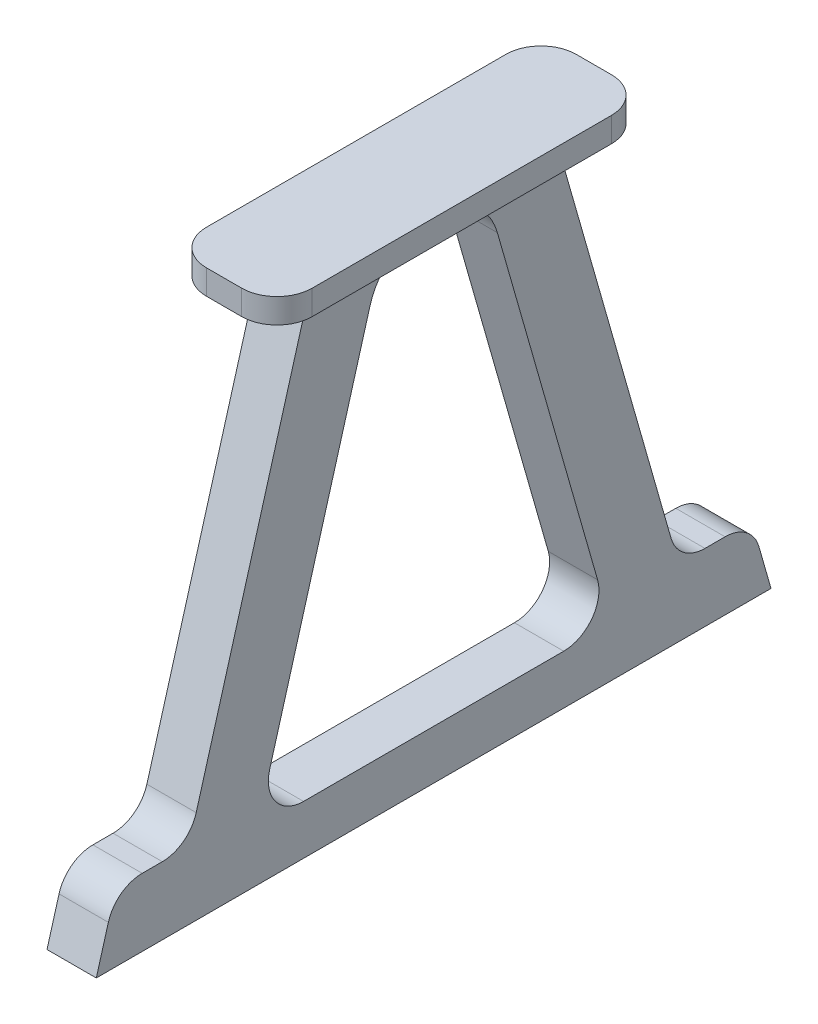
SolidWorks part; units mm, degrees
ref_plane "Front Plane" through (0, 0, 0) normal (0, 0, 1) x (1, 0, 0)
ref_plane "Top Plane" through (0, 0, 0) normal (0, 1, 0) x (1, 0, 0)
ref_plane "Right Plane" through (0, 0, 0) normal (1, 0, 0) x (0, 0, -1)
sketch "Sketch10" plane through (0, 0, 0) normal (0, 1, 0) x (1, 0, 0)
  line L5 (-5, -52.5) -> (5, -52.5)
  line L6 (-15, -42.5) -> (-15, 42.5)
  line L7 (-5, 52.5) -> (5, 52.5)
  line L8 (15, -42.5) -> (15, 42.5)
  line L9 (-15, -52.5) -> (15, 52.5) construction
  line L10 (-15, 52.5) -> (15, -52.5) construction
  arc A4 (5, -52.5) -> (15, -42.5) centre (5, -42.5) ccw
  arc A5 (-5, -52.5) -> (-15, -42.5) centre (-5, -42.5) cw
  arc A6 (5, 52.5) -> (15, 42.5) centre (5, 42.5) cw
  arc A7 (-15, 42.5) -> (-5, 52.5) centre (-5, 42.5) cw
  point P0 (0, 0)
  dimension "D3" = 10
  dimension "D1" = 105
  dimension "D2" = 30
extrude "Boss-Extrude3" add sketch "Sketch10" against normal blind 7
sketch "Sketch11" plane through (0, 0, 0) normal (1, 0, 0) x (0, 0, -1)
  line L0 (-35, -7) -> (35, -7)
  line L1 (-42.5, -7) -> (42.5, -7) construction
  line L2 (0, 0) -> (0, -258.7545) construction
  line L3 (-35, -7) -> (-75, -147)
  line L4 (-75, -147) -> (75, -147)
  line L5 (35, -7) -> (75, -147)
  line L6 (-75, -147) -> (-95.8003, -147)
  line L7 (-95.8003, -147) -> (-90.3059, -127.7695)
  line L8 (-90.3059, -127.7695) -> (-69.5056, -127.7695)
  line L9 (-71, -133) -> (71, -133)
  line L10 (69.5056, -127.7695) -> (90.3059, -127.7695)
  line L11 (90.3059, -127.7695) -> (95.8003, -147)
  line L12 (95.8003, -147) -> (75, -147)
  line L13 (-95.8003, -147) -> (-75, -147)
  line L14 (-14.1997, -7) -> (-50.1997, -133)
  line L15 (14.1997, -7) -> (50.1997, -133)
  line L16 (-42.5, 0) -> (42.5, 0) construction
  point P7 (0, -7)
  point P10 (0, -147)
  dimension "D1" = 70
  dimension "D2" = 140
  dimension "D3" = 150
  dimension "D4" = 20
  dimension "D5" = 20
  dimension "D6" = 20
  dimension "D7" = 20
  dimension "D8" = 14
  dimension "D9" = 20
  dimension "D10" = 20
  dimension "D11" = 191.6006
  dimension "D12" = 7
  dimension "D13" = 147
extrude "Boss-Extrude4" add sketch "Sketch11" along normal mid plane 14 contours L8 L7 L6 L3 | L2 L9 L3 L4 | L9 L2 L4 L5 | L14 L0 L3 L9 | L0 L15 L9 L5 | L12 L11 L10 L5 region at (0, -70, 42.5998) region at (0, -137.3848, 82.6529) region at (0, -140.0639, 36.5091) region at (0, -70, -42.5998) region at (0, -140.0639, -36.5091) region at (0, -137.3848, -82.6529)
fillet "Fillet2" radius 10 6 edges at (0, -127.7695, -90.3059) (0, -127.7695, -69.5056) (0, -133, -50.1997) (0, -133, 50.1997) (0, -127.7695, 69.5056) (0, -127.7695, 90.3059)
shell "Shell8" thickness 3 removed face at (0, -147, 0)
sketch "Sketch14" plane through (0, -147, 0) normal (0, -1, 0) x (1, 0, 0)
  line L1 (-4, 92.6803) -> (4, 92.6803)
  line L2 (-4, 92.6803) -> (-4, -92.6803)
  line L3 (-4, -92.6803) -> (4, -92.6803)
  line L4 (4, 92.6803) -> (4, -92.6803)
extrude "Boss-Extrude5" add sketch "Sketch14" against normal blind 4
fillet "Fillet5" 2 edges at (0, -7, 14.1997) (0, -7, -14.1997) type full round first side face at (0, -63.6264, 30.3787) second side face at (0, -63.6264, -30.3787) middle face at (0, -7, 24.5998)
